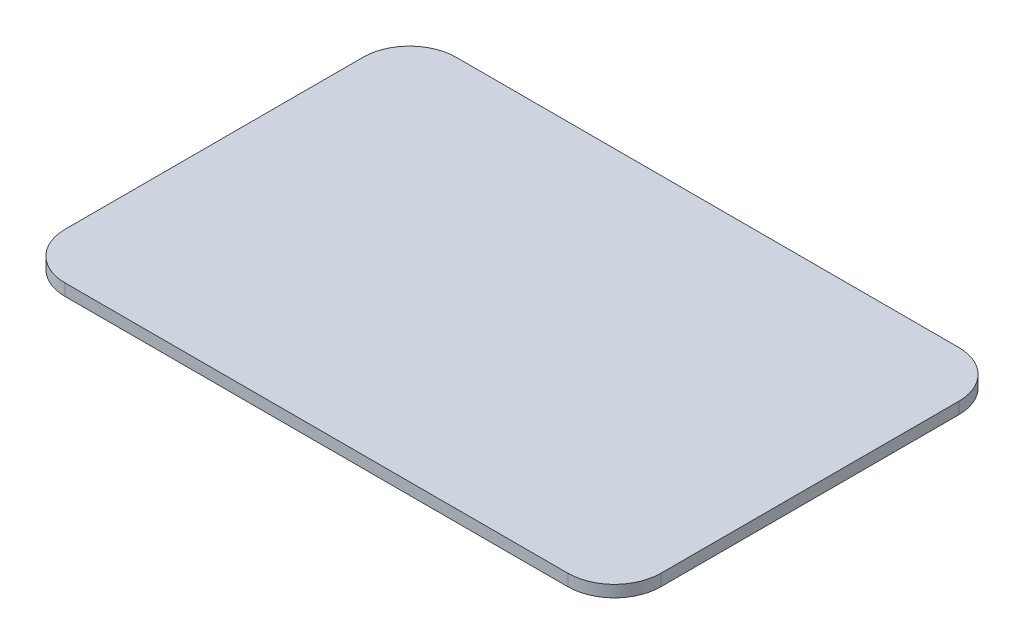
SolidWorks part; units mm, degrees
ref_plane "Front Plane" through (0, 0, 0) normal (0, 0, 1) x (1, 0, 0)
ref_plane "Top Plane" through (0, 0, 0) normal (0, 1, 0) x (1, 0, 0)
ref_plane "Right Plane" through (0, 0, 0) normal (1, 0, 0) x (0, 0, -1)
sketch "Sketch1" plane through (0, 0, 0) normal (0, 1, 0) x (1, 0, 0)
  line L1 (0, 0) -> (81.28, 0)
  line L2 (0, 0) -> (0, 53.34)
  line L3 (0, 53.34) -> (81.28, 53.34)
  line L4 (81.28, 0) -> (81.28, 53.34)
  dimension "D1" = 53.34
  dimension "D2" = 81.28
extrude "Boss-Extrude1" add sketch "Sketch1" along normal blind 1.6
fillet "Fillet1" radius 6.35 4 edges at (0, 0.8, -53.34) (81.28, 0.8, -53.34) (81.28, 0.8, 0) (0, 0.8, 0)
